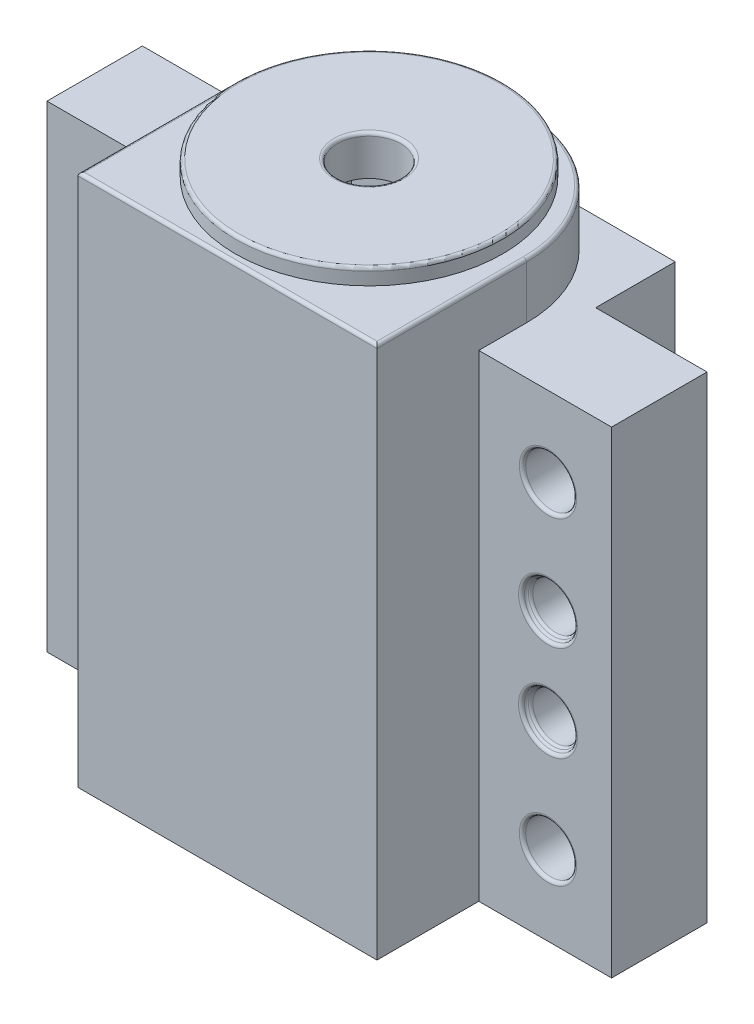
SolidWorks part; units mm, degrees
ref_plane "Front Plane" through (0, 0, 0) normal (0, 0, 1) x (1, 0, 0)
ref_plane "Top Plane" through (0, 0, 0) normal (0, 1, 0) x (1, 0, 0)
ref_plane "Right Plane" through (0, 0, 0) normal (1, 0, 0) x (0, 0, -1)
sketch "Main1" plane through (0, 0, 0) normal (0, 0, 1) x (1, 0, 0)
  line L1 (0, 0) -> (35.5, 0)
  line L2 (0, 0) -> (0, 30)
  line L3 (0, 30) -> (35.5, 30)
  line L4 (35.5, 0) -> (35.5, 30)
  dimension "D1" = 35.5
  dimension "D2" = 30
extrude "Main" add sketch "Main1" along normal blind 11 contours L3 L4 L1 L2
sketch "Sketch3" plane through (0, 0, 0) normal (0, 0, -1) x (-1, 0, 0)
  line L0 (-31.5, 30) -> (-31.5, 0) construction
  line L1 (0, 30) -> (-35.5, 30) construction
  line L2 (0, 0) -> (-35.5, 0) construction
  line L3 (-31.5, 15) -> (-17.75, 15) construction
  line L4 (-17.75, 15) -> (-17.75, 30) construction
  line L5 (-17.75, 15) -> (-4, 15) construction
  line L6 (-4, 30) -> (-4, 0) construction
  circle A0 centre (-31.5, 25) radius 1.6
  circle A1 centre (-31.5, 5) radius 1.6
  circle A2 centre (-4, 5) radius 1.6
  circle A3 centre (-4, 25) radius 1.6
  dimension "D2" = 3.2
  dimension "D1" = 27.5
  dimension "D3" = 5
  dimension "D4" = 5
extrude "Cut-Extrude1" cut sketch "Sketch3" against normal up to next
sketch "Adjustable Standoff Heat Sets" plane through (0, 0, 11) normal (0, 0, 1) x (1, 0, 0)
  line L0 (4, 25) -> (4, 5) construction
  line L1 (17.75, 30) -> (17.75, 0) construction
  line L2 (0, 30) -> (35.5, 30) construction
  line L3 (0, 0) -> (35.5, 0) construction
  point P10 (4, 18)
  point P11 (4, 12)
  point P12 (31.5, 12)
  point P13 (31.5, 18)
  dimension "D1" = 7
  dimension "D2" = 7
hole_wizard "M2 Heat Sets" positions "3DSketch1" profile "Sketch6" counterbore size "M72" standard "ANSI Metric"
sketch3d "3DSketch1"
  point P0 (4, 18, 11)
  point P3 (4, 12, 11)
  point P6 (31.5, 18, 11)
  point P9 (31.5, 12, 11)
sketch "Sketch6" plane through (4, 18, 11) normal (1, 0, 0) x (0, -1, 0)
  line L0 (0, 0) -> (0, 6)
  line L1 (0, 6) -> (1.45, 6)
  line L2 (1.45, 6) -> (1.45, 0.3)
  line L3 (1.45, 0.3) -> (1.65, 0.3)
  line L4 (1.65, 0.3) -> (1.65, 0)
  line L5 (1.65, 0) -> (0, 0)
  line L10 (0, 6) -> (-1.45, 6) construction
  line L11 (0, -6.35) -> (0, 107.95) construction
  dimension "Hole Dia." = 2.9
  dimension "Hole Depth" = 6
  dimension "C'Bore Dia." = 3.3
  dimension "C'Bore Depth" = 0.3
  dimension "Drill Angle" = 180
sketch "Sketch7" plane through (0, 0, 0) normal (0, 0, -1) x (-1, 0, 0)
  line L0 (-31.5, 28) -> (-35.5, 28) construction
  line L1 (-35.5, 0) -> (-35.5, 30) construction
  line L2 (-28.5, 25) -> (-28.5, 5) construction
  line L3 (-31.5, 2) -> (-35.5, 2) construction
  line L4 (-35.5, 28) -> (-35.5, 2) construction
  line L5 (-17.75, 30) -> (-17.75, 0) construction
  line L6 (0, 30) -> (-35.5, 30) construction
  line L7 (0, 0) -> (-35.5, 0) construction
  line L8 (-4, 2) -> (0, 2) construction
  line L9 (0, 28) -> (0, 2) construction
  line L10 (-4, 28) -> (0, 28) construction
  line L11 (-7, 25) -> (-7, 5) construction
  line L12 (0, 0) -> (-7, 0)
  line L13 (-35.5, 30) -> (-28.5, 30)
  line L14 (-35.5, 30) -> (-35.5, 0)
  line L15 (-35.5, 0) -> (-28.5, 0)
  line L16 (-28.5, 30) -> (-28.5, 0)
  line L17 (-7, 30) -> (-7, 0)
  line L18 (0, 30) -> (-7, 30)
  line L19 (0, 30) -> (0, 0)
  arc A0 (-28.5, 25) -> (-31.5, 28) centre (-31.5, 25) ccw construction
  arc A1 (-31.5, 2) -> (-28.5, 5) centre (-31.5, 5) ccw
  circle A2 centre (-4, 25) radius 3 construction
  circle A3 centre (-4, 5) radius 3 construction
  arc A4 (-31.5, 28) -> (-28.5, 25) centre (-31.5, 25) ccw construction
  arc A5 (-28.5, 5) -> (-31.5, 2) centre (-31.5, 5) ccw construction
  arc A6 (-7, 25) -> (-4, 28) centre (-4, 25) cw construction
  arc A7 (-4, 2) -> (-7, 5) centre (-4, 5) cw construction
  circle M10 centre (-4, 25) radius 1.6
  circle M11 centre (-4, 5) radius 1.6
  circle M12 centre (-31.5, 5) radius 1.6
  circle M13 centre (-31.5, 25) radius 1.6
  line M14 (0, 0) -> (0, 30)
  line M15 (0, 30) -> (-35.5, 30)
  line M16 (-35.5, 30) -> (-35.5, 0)
  line M17 (-35.5, 0) -> (0, 0)
  dimension "D1" = 6
extrude "Countersink" cut sketch "Sketch7" against normal blind 5 contours L16 M15 M16 M17 M13 M12 | L17 M15 M17 M14 M10 M11 region at (3.4585, 15, 0) region at (32.0415, 15, 0)
sketch "Sketch8" plane through (0, 0, 11) normal (0, 0, 1) x (1, 0, 0)
  line L0 (0, 30) -> (35.5, 30) construction
  line L1 (8.35, 30) -> (27.15, 30)
  line L2 (8.35, 30) -> (8.35, 0)
  line L3 (8.35, 0) -> (27.15, 0)
  line L4 (27.15, 30) -> (27.15, 0)
  line L5 (8.35, 30) -> (0, 30) construction
  line L6 (27.15, 30) -> (35.5, 30) construction
  line L7 (0, 0) -> (35.5, 0) construction
  dimension "D1" = 18.8
extrude "Motor Hold" add sketch "Sketch8" along normal blind 6.4
sketch "Sketch9" plane through (0, 0, 0) normal (0, 0, -1) x (-1, 0, 0)
  line L0 (-7, 30) -> (-28.5, 30) construction
  line L1 (-23.75, 30) -> (-11.75, 30)
  line L2 (-23.75, 30) -> (-23.75, 23)
  line L3 (-23.75, 23) -> (-11.75, 23)
  line L4 (-11.75, 30) -> (-11.75, 23)
  line L5 (-23.75, 26.5) -> (-28.5, 26.5) construction
  line L6 (-28.5, 30) -> (-28.5, 0) construction
  line L7 (-11.75, 26.5) -> (-7, 26.5) construction
  line L8 (-7, 30) -> (-7, 0) construction
  line L11 (-25.25, 11.5) -> (-28.5, 11.5) construction
  line L12 (-25.25, 23) -> (-10.25, 23)
  line L13 (-25.25, 23) -> (-25.25, 0)
  line L14 (-25.25, 0) -> (-10.25, 0)
  line L15 (-10.25, 23) -> (-10.25, 0)
  line L16 (-10.25, 11.5) -> (-7, 11.5) construction
  line L17 (-7, 0) -> (-28.5, 0) construction
  line M11 (-7, 30) -> (-28.5, 30)
  line M13 (-28.5, 0) -> (-7, 0)
  dimension "D1" = 12
  dimension "D2" = 7
  dimension "D3" = 15
extrude "Motor Clearance" cut sketch "Sketch9" against normal blind 13.6 contours L15 L12 L3 L13 M13 | L4 L2 L3 M11 region at (17.75, 26.5, 0) region at (17.75, 11.5, 0)
sketch "Motor Mount Plate" plane through (0, 30, 0) normal (0, 1, 0) x (1, 0, 0)
  line L0 (27.15, -17.4) -> (27.15, 0) construction
  line L1 (8.35, -17.4) -> (27.15, -17.4)
  line L2 (8.35, -17.4) -> (8.35, 0)
  line L3 (8.35, 0) -> (27.15, 0)
  line L4 (27.15, -17.4) -> (27.15, 0)
  line L6 (7, 0) -> (11.75, 0) construction
extrude "Motor Mount" add sketch "Motor Mount Plate" along normal blind 3.5
sketch "Sketch12" plane through (0, 30, 0) normal (0, -1, 0) x (1, 0, 0)
  line L0 (17.75, 13.6) -> (17.75, 8.5) construction
  line L1 (11.75, 13.6) -> (23.75, 13.6) construction
  line L2 (17.75, 8.5) -> (22.25, 8.5) construction
  line L3 (17.75, 8.5) -> (13.25, 8.5) construction
  circle A2 centre (17.75, 8.5) radius 2
  dimension "D4" = 4
  dimension "D1" = 5.1
  dimension "D2" = 9
extrude "Mount Holes" cut sketch "Sketch12" against normal up to next
sketch "Sketch14" plane through (0, 23, 0) normal (0, -1, 0) x (1, 0, 0)
  line L0 (28.5, 5) -> (28.5, 0) construction
  line L1 (7, 0) -> (28.5, 0)
  line L2 (7, 0) -> (7, 3.6)
  line L3 (7, 3.6) -> (28.5, 3.6)
  line L4 (28.5, 0) -> (28.5, 3.6)
  line L5 (11.75, 13.6) -> (23.75, 13.6) construction
  dimension "D1" = 10
extrude "Top" add sketch "Sketch14" against normal up to surface (7 mm away) up to face at (17.75, 30, 6.5)
sketch "Sketch15" plane through (0, 33.5, 0) normal (0, 1, 0) x (1, 0, 0)
  circle A0 centre (17.75, -8.5) radius 8.4
  circle A3 centre (17.75, -8.5) radius 2 construction
  circle A4 centre (17.75, -8.5) radius 2
  dimension "D1" = 16.8
extrude "Anti-Rub Spacer" add sketch "Sketch15" along normal blind 1
fillet "Fillet2" radius 8 2 edges at (27.15, 31.75, 0) (8.35, 31.75, 0)
ref_plane "Plane1" through (0, 34.5, 0) normal (0, 1, 0) x (1, 0, 0)
fillet "Fillet6" radius 0.2 2 edges at (32.95, 12, 5) (33.15, 12, 11)
fillet "Fillet7" radius 0.2 1 edges at (32.95, 12, 10.7)
fillet "Fillet8" radius 0.2 9 edges at (33.15, 12, 10.7) (10.6931, 33.5, 2.3431) (24.8069, 33.5, 2.3431) (17.75, 34.5, 16.9) (17.75, 33.5, 0) (8.35, 33.5, 12.7) (17.75, 33.5, 17.4) (27.15, 33.5, 12.7) (17.75, 34.5, 10.5)
fillet "Fillet10" radius 0.2 1 edges at (5.45, 18, 10.7)
fillet "Fillet11" radius 0.2 3 edges at (5.65, 18, 10.7) (5.45, 12, 5) (5.65, 12, 11)
fillet "Fillet12" radius 0.2 1 edges at (5.45, 12, 10.7)
fillet "Fillet13" radius 0.2 3 edges at (5.65, 12, 10.7) (32.95, 18, 5) (33.15, 18, 11)
fillet "Fillet14" radius 0.2 1 edges at (32.95, 18, 10.7)
fillet "Fillet15" radius 0.2 1 edges at (33.15, 18, 10.7)
fillet "Fillet16" radius 0.2 4 edges at (2.4, 25, 11) (2.4, 5, 11) (29.9, 5, 11) (29.9, 25, 11)
chamfer "Chamfer1" distance 1.7 angle 40 4 edges at (29.9, 25, 5) (2.4, 5, 5) (2.4, 25, 5) (29.9, 5, 5) first distance on face at (29.9, 25, 10.8) first distance on face at (2.4, 5, 10.8) first distance on face at (2.4, 25, 10.8) first distance on face at (29.9, 5, 10.8)
sketch "Sketch17" plane through (0, 0, 13.6) normal (0, 0, -1) x (-1, 0, 0)
  line L0 (-25.25, 0) -> (-10.25, 0) construction
  line L1 (-25.25, 23) -> (-23.8, 23)
  line L2 (-25.25, 23) -> (-25.25, 0)
  line L3 (-25.25, 0) -> (-23.8, 0)
  line L4 (-23.8, 23) -> (-23.8, 0)
  line L6 (-10.25, 23) -> (-11.7, 23)
  line L7 (-10.25, 23) -> (-10.25, 0)
  line L8 (-10.25, 0) -> (-11.7, 0)
  line L9 (-11.7, 23) -> (-11.7, 0)
  dimension "D1" = 12.1
extrude "Boss-Extrude1" add sketch "Sketch17" along normal blind 10
chamfer "Chamfer2" distance 1.5 angle 45 2 edges at (23.8, 11.5, 3.6) (11.7, 11.5, 3.6)
sketch "Sketch18" plane through (0, 30, 0) normal (0, -1, 0) x (1, 0, 0)
  line L1 (11.75, 13.6) -> (23.75, 13.6)
  line L2 (11.75, 13.6) -> (11.75, 3.6)
  line L3 (11.75, 3.6) -> (23.75, 3.6)
  line L4 (23.75, 13.6) -> (23.75, 3.6)
extrude "Cut-Extrude2" cut sketch "Sketch18" against normal blind 2
